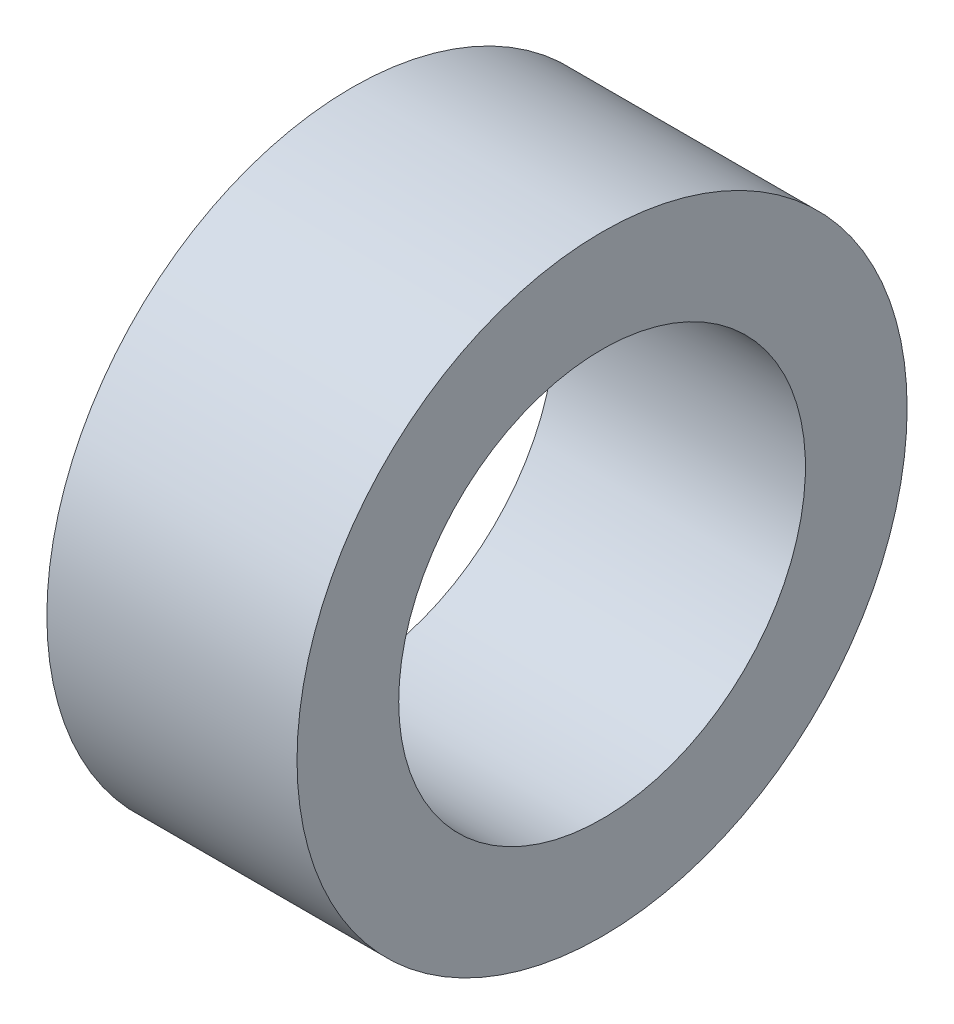
SolidWorks part; units mm, degrees
material "AISI 1020 Steel, Cold Rolled"
ref_plane "Front Plane" through (0, 0, 0) normal (0, 0, 1) x (1, 0, 0)
ref_plane "Top Plane" through (0, 0, 0) normal (0, 1, 0) x (1, 0, 0)
ref_plane "Right Plane" through (0, 0, 0) normal (1, 0, 0) x (0, 0, -1)
sketch "Sketch1" plane through (0, 0, 0) normal (1, 0, 0) x (0, 0, -1)
  circle A0 centre (0, 0) radius 6.35
  circle A1 centre (0, 0) radius 9.525
  dimension "D1" = 12.7
  dimension "D2" = 19.05
extrude "Boss-Extrude1" add sketch "Sketch1" along normal blind 7.8105
